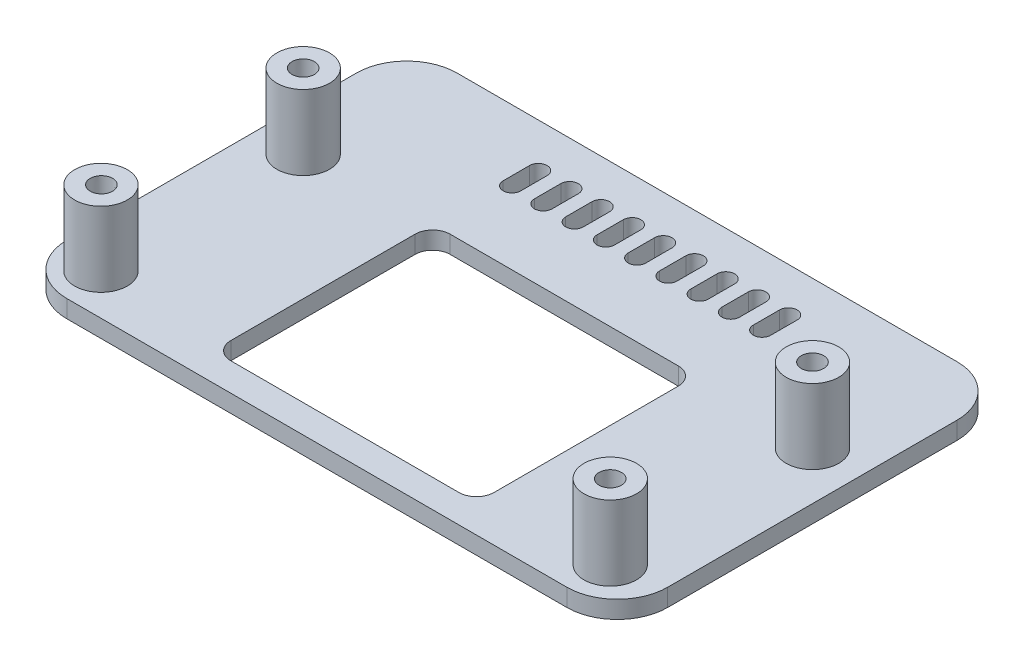
SolidWorks part; units mm, degrees
ref_plane "前视基准面" through (0, 0, 0) normal (0, 0, 1) x (1, 0, 0)
ref_plane "上视基准面" through (0, 0, 0) normal (0, 1, 0) x (1, 0, 0)
ref_plane "右视基准面" through (0, 0, 0) normal (1, 0, 0) x (0, 0, -1)
other "Configuration Table"
sketch "草图1" plane through (0, 0, 0) normal (0, 1, 0) x (1, 0, 0)
  line L1 (-34.4994, 19.3243) -> (34.0006, 19.3243)
  line L2 (-34.4994, 19.3243) -> (-34.4994, -25.1757)
  line L3 (-34.4994, -25.1757) -> (34.0006, -25.1757)
  line L4 (34.0006, 19.3243) -> (34.0006, -25.1757)
  dimension "D1" = 68.5
  dimension "D2" = 44.5
extrude "凸台-拉伸1" add sketch "草图1" along normal blind 2
fillet "圆角1" radius 5.75 4 edges at (34.0006, 1, -19.3243) (34.0006, 1, 25.1757) (-34.4994, 1, 25.1757) (-34.4994, 1, -19.3243)
sketch "草图2" plane through (0, 0, 0) normal (0, -1, 0) x (1, 0, 0)
  line L0 (-28.7494, 25.1757) -> (28.2506, 25.1757) construction
  line L1 (-15.2494, 21.9757) -> (14.7506, 21.9757)
  line L2 (-15.2494, 21.9757) -> (-15.2494, -3.0243)
  line L3 (-15.2494, -3.0243) -> (14.7506, -3.0243)
  line L4 (14.7506, 21.9757) -> (14.7506, -3.0243)
  line L5 (-15.2494, 21.9757) -> (14.7506, -3.0243) construction
  line L6 (-15.2494, -3.0243) -> (14.7506, 21.9757) construction
  point P0 (-0.2494, 9.4757)
  point P8 (-0.2494, 25.1757)
  dimension "D1" = 15.7
  dimension "D2" = 30
  dimension "D3" = 25
extrude "切除-拉伸1" cut sketch "草图2" against normal through all
fillet "圆角2" radius 2 4 edges at (-15.2494, 1, -3.0243) (-15.2494, 1, 21.9757) (14.7506, 1, 21.9757) (14.7506, 1, -3.0243)
sketch "草图3" plane through (0, 2, 0) normal (0, 1, 0) x (1, 0, 0)
  circle A0 centre (-29.5244, 2.5493) radius 3
  circle A1 centre (-29.5244, -20.5007) radius 3
  circle A2 centre (28.5006, -20.4757) radius 3
  circle A3 centre (28.5256, 2.5493) radius 3
  dimension "D1" = 6
extrude "凸台-拉伸2" add sketch "草图3" along normal blind 8.5
sketch "草图4" plane through (0, 10.5, 0) normal (0, 1, 0) x (1, 0, 0)
  circle A0 centre (-29.5244, 2.5493) radius 1.275
  circle A1 centre (-29.4994, -20.4757) radius 1.275
  circle A2 centre (28.5256, -20.5007) radius 1.275
  circle A3 centre (28.5256, 2.5493) radius 1.275
  dimension "D1" = 2.55
extrude "切除-拉伸2" cut sketch "草图4" against normal blind 6 draft 1
sketch "草图5" plane through (0, 0, 0) normal (0, -1, 0) x (1, 0, 0)
  line L0 (-14.4994, -11.3243) -> (-14.4994, -14.3243) construction
  line L1 (-13.4994, -11.3243) -> (-13.4994, -14.3243)
  line L2 (-15.4994, -11.3243) -> (-15.4994, -14.3243)
  line L3 (-10.9369, -11.3243) -> (-10.9369, -14.3243) construction
  line L4 (-9.9369, -11.3243) -> (-9.9369, -14.3243)
  line L5 (-11.9369, -11.3243) -> (-11.9369, -14.3243)
  line L6 (-7.3744, -11.3243) -> (-7.3744, -14.3243) construction
  line L7 (-6.3744, -11.3243) -> (-6.3744, -14.3243)
  line L8 (-8.3744, -11.3243) -> (-8.3744, -14.3243)
  line L9 (-3.8119, -11.3243) -> (-3.8119, -14.3243) construction
  line L10 (-2.8119, -11.3243) -> (-2.8119, -14.3243)
  line L11 (-4.8119, -11.3243) -> (-4.8119, -14.3243)
  line L12 (-0.2494, -11.3243) -> (-0.2494, -14.3243) construction
  line L13 (0.7506, -11.3243) -> (0.7506, -14.3243)
  line L14 (-1.2494, -11.3243) -> (-1.2494, -14.3243)
  line L15 (3.3131, -11.3243) -> (3.3131, -14.3243) construction
  line L16 (4.3131, -11.3243) -> (4.3131, -14.3243)
  line L17 (2.3131, -11.3243) -> (2.3131, -14.3243)
  line L18 (6.8756, -11.3243) -> (6.8756, -14.3243) construction
  line L19 (7.8756, -11.3243) -> (7.8756, -14.3243)
  line L20 (5.8756, -11.3243) -> (5.8756, -14.3243)
  line L21 (10.4381, -11.3243) -> (10.4381, -14.3243) construction
  line L22 (11.4381, -11.3243) -> (11.4381, -14.3243)
  line L23 (9.4381, -11.3243) -> (9.4381, -14.3243)
  line L24 (14.0006, -11.3243) -> (14.0006, -14.3243) construction
  line L25 (15.0006, -11.3243) -> (15.0006, -14.3243)
  line L26 (13.0006, -11.3243) -> (13.0006, -14.3243)
  line L27 (28.2506, -19.3243) -> (-28.7494, -19.3243) construction
  line L28 (-34.4994, -13.5743) -> (-34.4994, 19.4257) construction
  line L29 (34.0006, 19.4257) -> (34.0006, -13.5743) construction
  arc A0 (-13.4994, -11.3243) -> (-15.4994, -11.3243) centre (-14.4994, -11.3243) ccw
  arc A1 (-15.4994, -14.3243) -> (-13.4994, -14.3243) centre (-14.4994, -14.3243) ccw
  arc A2 (-9.9369, -11.3243) -> (-11.9369, -11.3243) centre (-10.9369, -11.3243) ccw
  arc A3 (-11.9369, -14.3243) -> (-9.9369, -14.3243) centre (-10.9369, -14.3243) ccw
  arc A4 (-6.3744, -11.3243) -> (-8.3744, -11.3243) centre (-7.3744, -11.3243) ccw
  arc A5 (-8.3744, -14.3243) -> (-6.3744, -14.3243) centre (-7.3744, -14.3243) ccw
  arc A6 (-2.8119, -11.3243) -> (-4.8119, -11.3243) centre (-3.8119, -11.3243) ccw
  arc A7 (-4.8119, -14.3243) -> (-2.8119, -14.3243) centre (-3.8119, -14.3243) ccw
  arc A8 (0.7506, -11.3243) -> (-1.2494, -11.3243) centre (-0.2494, -11.3243) ccw
  arc A9 (-1.2494, -14.3243) -> (0.7506, -14.3243) centre (-0.2494, -14.3243) ccw
  arc A10 (4.3131, -11.3243) -> (2.3131, -11.3243) centre (3.3131, -11.3243) ccw
  arc A11 (2.3131, -14.3243) -> (4.3131, -14.3243) centre (3.3131, -14.3243) ccw
  arc A12 (7.8756, -11.3243) -> (5.8756, -11.3243) centre (6.8756, -11.3243) ccw
  arc A13 (5.8756, -14.3243) -> (7.8756, -14.3243) centre (6.8756, -14.3243) ccw
  arc A14 (11.4381, -11.3243) -> (9.4381, -11.3243) centre (10.4381, -11.3243) ccw
  arc A15 (9.4381, -14.3243) -> (11.4381, -14.3243) centre (10.4381, -14.3243) ccw
  arc A16 (15.0006, -11.3243) -> (13.0006, -11.3243) centre (14.0006, -11.3243) ccw
  arc A17 (13.0006, -14.3243) -> (15.0006, -14.3243) centre (14.0006, -14.3243) ccw
  point P2 (-14.4994, -12.8243)
  point P10 (-10.9369, -12.8243)
  point P17 (-7.3744, -12.8243)
  point P24 (-3.8119, -12.8243)
  point P31 (-0.2494, -12.8243)
  point P38 (3.3131, -12.8243)
  point P45 (6.8756, -12.8243)
  point P52 (10.4381, -12.8243)
  point P59 (14.0006, -12.8243)
  dimension "D1" = 1
  dimension "D2" = 3
  dimension "D4" = 20
  dimension "D5" = 20
  dimension "D6" = 5
  dimension "D3" = 9
extrude "切除-拉伸3" cut sketch "草图5" against normal blind 10
